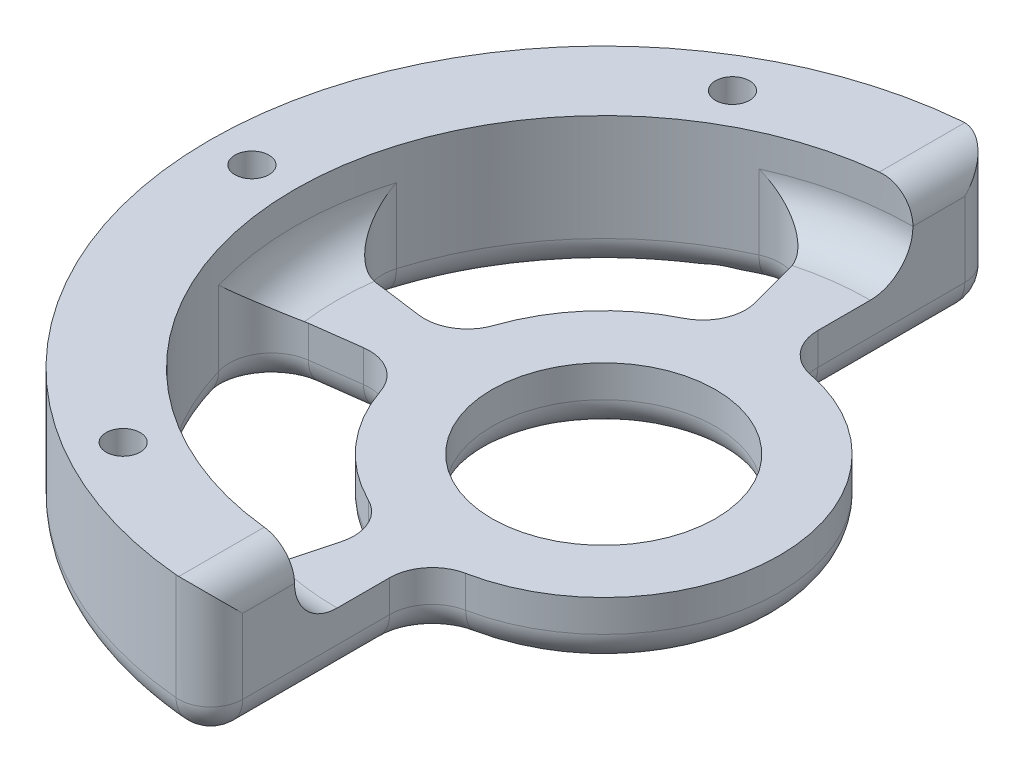
SolidWorks part; units mm, degrees
ref_plane "Front Plane" through (0, 0, 0) normal (0, 0, 1) x (1, 0, 0)
ref_plane "Top Plane" through (0, 0, 0) normal (0, 1, 0) x (1, 0, 0)
ref_plane "Right Plane" through (0, 0, 0) normal (1, 0, 0) x (0, 0, -1)
sketch "Sketch1" plane through (0, 0, 0) normal (0, 1, 0) x (1, 0, 0)
  line L0 (-13.0077, -7.51) -> (43288.2625, 24992.49) construction
  line L1 (0, -15.02) -> (0, 49984.98) construction
  line L2 (-32.0776, -18.52) -> (-25.1494, -14.52)
  line L3 (0, -37.04) -> (0, -29.04)
  line L4 (0, 0) -> (-25000, -43301.2702) construction
  line L5 (-32.0776, -18.52) -> (-25.1494, -14.52)
  line L6 (-32.0776, 18.52) -> (-25.1494, 14.52)
  line L7 (-32.0776, 18.52) -> (-25.1494, 14.52)
  line L8 (0, 37.04) -> (0, 29.04)
  circle A0 centre (0, 0) radius 37.04 construction
  circle A1 centre (0, 0) radius 33.04 construction
  circle A2 centre (0, 0) radius 29.04 construction
  arc A3 (-25.1494, -14.52) -> (0, -29.04) centre (0, 0) ccw
  arc A4 (0, -37.04) -> (-32.0776, -18.52) centre (0, 0) cw
  circle A5 centre (-16.52, -28.6135) radius 1.6
  arc A6 (-25.1494, 14.52) -> (-25.1494, -14.52) centre (0, 0) ccw
  arc A7 (-32.0776, -18.52) -> (-32.0776, 18.52) centre (0, 0) cw
  circle A8 centre (-33.04, 0) radius 1.6
  arc A9 (0, 29.04) -> (-25.1494, 14.52) centre (0, 0) ccw
  arc A10 (-32.0776, 18.52) -> (0, 37.04) centre (0, 0) cw
  circle A11 centre (-16.52, 28.6135) radius 1.6
  point P13 (-16.52, -28.6135)
  point P33 (0, 0)
  dimension "D1" = 58.08
  dimension "D2" = 66.08
  dimension "D3" = 74.08
  dimension "D5" = 3.2
  dimension "D4" = 60
  dimension "D6" = 30
  dimension "D7" = 3
extrude "Boss-Extrude1" add sketch "Sketch1" along normal blind 7 contours A4 L3 A3 L2 A5 | A7 L2 A6 L6 A8 | A10 L6 A9 L8 A11 region at (-36.651, 0, 0) region at (-28.4175, 0, 16.8594) region at (-18.324, 0, -31.7382)
sketch "Sketch2" plane through (0, 0, 0) normal (0, -1, 0) x (1, 0, 0)
  line L0 (0, -29.04) -> (0, -16.5)
  line L1 (-4.2705, -15.9378) -> (-7.5161, -28.0505)
  line L2 (-28.7916, -3.7905) -> (-16.3588, -2.1537)
  line L3 (-16.3588, 2.1537) -> (-28.7916, 3.7905)
  line L4 (-7.5161, 28.0505) -> (-4.2705, 15.9378)
  line L5 (0, 16.5) -> (0, 29.04)
  line L6 (0, 37.04) -> (0, 29.04) construction
  line L7 (0, 0) -> (-25000, -43301.2702) construction
  line L8 (0, 0) -> (-30438.0715, -39667.667) construction
  line L9 (0, 0) -> (-19134.1716, -46193.9766) construction
  line L10 (-11.1131, -26.8295) -> (-14.1746, -34.2205)
  line L11 (-22.5485, -29.3858) -> (-17.6784, -23.039)
  line L12 (-36.7231, 4.8347) -> (-28.7916, 3.7905)
  line L13 (-28.7916, -3.7905) -> (-36.7231, -4.8347)
  line L14 (-14.1746, 34.2205) -> (-11.1131, 26.8295)
  line L15 (-17.6784, 23.039) -> (-22.5485, 29.3858)
  line L16 (0, 0) -> (-50000, 0) construction
  circle A0 centre (0, 0) radius 10.5
  circle A1 centre (0, 0) radius 16.5
  arc A2 (0, 29.04) -> (0, -29.04) centre (0, 0) ccw construction
  arc A3 (-7.5161, -28.0505) -> (0, -29.04) centre (0, 0) ccw
  arc A4 (-28.7916, 3.7905) -> (-28.7916, -3.7905) centre (0, 0) ccw
  arc A5 (0, 29.04) -> (-7.5161, 28.0505) centre (0, 0) ccw
  arc A6 (-22.5485, -29.3858) -> (-14.1746, -34.2205) centre (0, 0) ccw
  arc A7 (-17.6784, -23.039) -> (-11.1131, -26.8295) centre (0, 0) ccw
  arc A8 (0, 37.04) -> (0, -37.04) centre (0, 0) ccw construction
  arc A9 (-28.7916, 3.7905) -> (-28.7916, -3.7905) centre (0, 0) ccw
  arc A10 (-36.7231, 4.8347) -> (-36.7231, -4.8347) centre (0, 0) ccw
  arc A11 (-11.1131, 26.8295) -> (-17.6784, 23.039) centre (0, 0) ccw
  arc A12 (-14.1746, 34.2205) -> (-22.5485, 29.3858) centre (0, 0) ccw
  circle A13 centre (-16.52, -28.6135) radius 3.25
  circle A14 centre (-33.04, 0) radius 3.25
  circle A15 centre (-16.52, 28.6135) radius 3.25
  point P22 (0, 0)
  point P47 (0, 0)
  point P50 (-37.04, 0)
  circle M6 centre (-16.52, 28.6135) radius 1.6
  arc M7 (0, 37.04) -> (0, -37.04) centre (0, 0) ccw
  line M8 (0, -37.04) -> (0, -29.04)
  arc M9 (0, -29.04) -> (0, 29.04) centre (0, 0) cw
  line M10 (0, 29.04) -> (0, 37.04)
  circle M11 centre (-33.04, 0) radius 1.6
  circle M12 centre (-16.52, -28.6135) radius 1.6
  dimension "D1" = 21
  dimension "D2" = 6
  dimension "D8" = 6.5
  dimension "D3" = 15
  dimension "D4" = 3
  dimension "D5" = 7.5
  dimension "D6" = 7.5
  dimension "D7" = 3
extrude "Boss-Extrude2" add sketch "Sketch2" along normal blind 6 contours A1 L5 L4 M9 | A1 L3 L2 M9 | A1 A0 | A1 L1 L0 M9 | M10 M7 M8 M9 M12 M11 M6 | L10 M9 M7 M8 | L11 L10 M7 M9 M12 | L13 L11 M9 M7 | L15 L12 M9 M7 | L14 M7 M9 M10 | L15 L14 M9 M7 M6 region at (-3.0385, 0, -23.0797) region at (-6.4357, 0, -32.3546) region at (-2.0928, 0, -15.8961) region at (-12.7916, 0, -30.4638) region at (-23.2789, 0, 0) region at (-3.0385, 0, 23.0797) region at (-28.0199, 0, -16.1773) region at (-32.7739, 0, -4.1866) region at (-6.4357, 0, 32.3546) region at (-28.0199, 0, 16.1773) region at (-19.9866, 0, 26.3098)
fillet "Fillet1" radius 4 13 edges at (-7.5161, -3, 28.0505) (-3.7905, 0, 28.7916) (-28.7916, -3, 3.7905) (-28.7916, -3, -3.7905) (-29.04, 0, 0) (-7.5161, -3, -28.0505) (-3.7905, 0, -28.7916) (0, -3, -16.5) (0, -3, 16.5) (-4.2705, -3, 15.9378) (-16.3588, -3, 2.1537) (-16.3588, -3, -2.1537) (-4.2705, -3, -15.9378)
sketch "Sketch4" plane through (0, -6, 0) normal (0, -1, 0) x (1, 0, 0)
  line L0 (-5.4376, 30.8379) -> (8676.9713, -49209.5497) construction
  line L1 (0, 0) -> (0, 50000) construction
  line L2 (-5.7373, -969.4347) -> (-5.7373, 49030.5653) construction
  circle A0 centre (-5.7373, 32.538) radius 2.25
  circle A1 centre (0, 0) radius 33.04 construction
  circle A2 centre (-29.5256, 14.8283) radius 2.25
  circle A3 centre (-29.5256, -14.8283) radius 2.25
  circle A4 centre (-5.7373, -32.538) radius 2.25
  point P20 (0, 0)
  dimension "D1" = 66.08
  dimension "D2" = 4.5
  dimension "D3" = 10
  dimension "D4" = 4
extrude "Cut-Extrude2" cut sketch "Sketch4" against normal blind 10
fillet "Fillet2" radius 3 27 edges at (-37.04, -6, 0) (0, 7, -33.04) (0, 7, 33.04) (0, -6, -28.573) (0.9079, -6, -17.5684) (16.5, -6, 0) (0.9079, -6, 17.5684) (-22.2205, -6, 2.9254) (-17.2996, -6, 3.1933) (-12.4054, -6, 10.8792) (-5.424, -6, 16.7348) (-5.8007, -6, 21.6485) (-8.5453, -6, 26.4541) (-21.8334, -6, 19.1474) (-8.5453, -6, -26.4541) (-5.8007, -6, -21.6485) (-5.424, -6, -16.7348) (-12.4054, -6, -10.8792) (-17.2996, -6, -3.1933) (-22.2205, -6, -2.9254) (-27.3432, -6, -5.0193) (0, -6, 28.573) (-27.3432, -6, 5.0193) (-21.8334, -6, -19.1474) (0, 0.5, -37.04) (0, 0.5, 37.04) (0, -6, -10.5)
